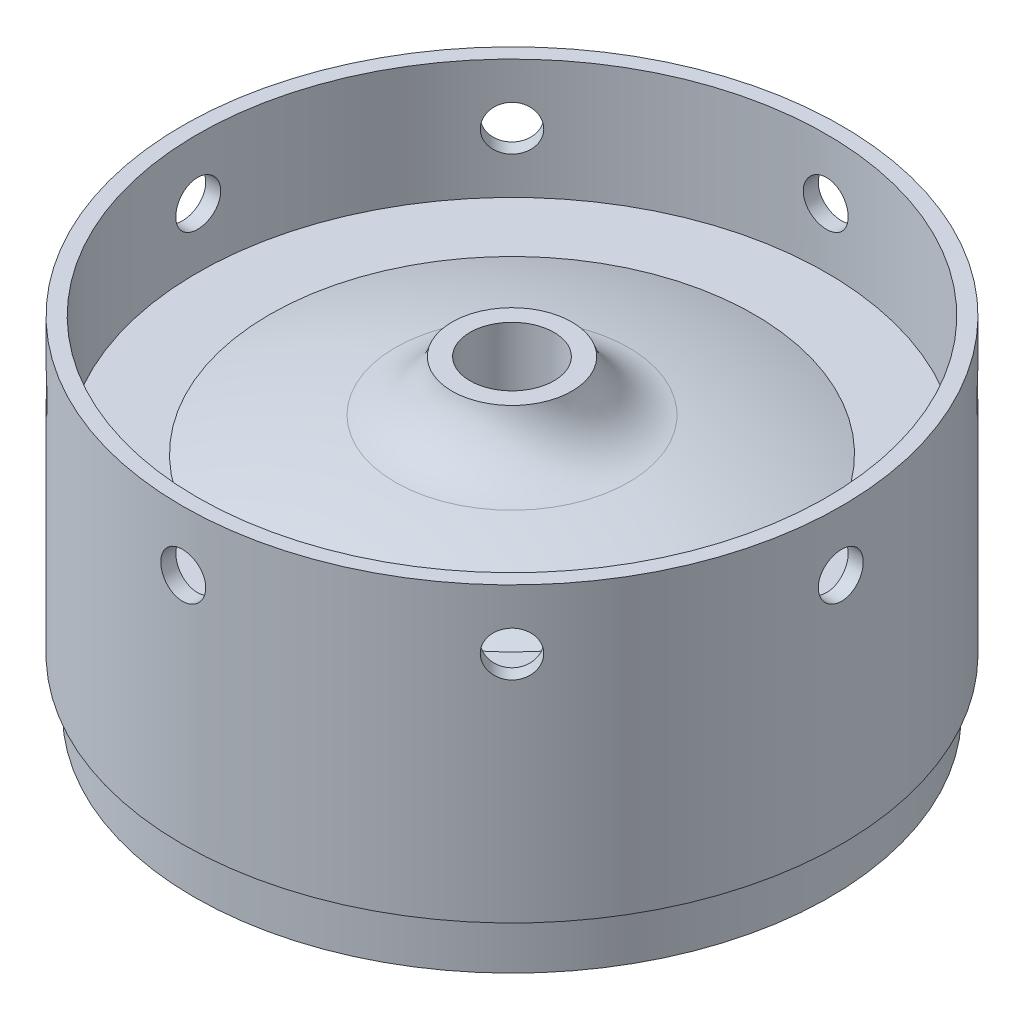
SolidWorks part; units mm, degrees
material "6061-T6 (SS)"
ref_plane "Front Plane" through (0, 0, 0) normal (0, 0, 1) x (1, 0, 0)
ref_plane "Top Plane" through (0, 0, 0) normal (0, 1, 0) x (1, 0, 0)
ref_plane "Right Plane" through (0, 0, 0) normal (1, 0, 0) x (0, 0, -1)
ref_axis "Axis1" through (0, 127.061, 0) along (0, -1, 0)
sketch "Sketch1" plane through (0, 0, 0) normal (0, 0, 1) x (1, 0, 0)
  line L0 (-69.85, 10.9548) -> (-69.85, 73.025)
  line L1 (-67.3735, 9.525) -> (-69.85, 10.9548)
  line L2 (0, 127.061) -> (0, -81.9141) construction
  line L3 (-8.9065, 65.553) -> (-12.7, 65.553)
  line L4 (-67.3735, 9.525) -> (-67.3735, 0)
  line L5 (-67.3735, 0) -> (-65.786, 0)
  line L6 (55, 0) -> (-55, 0) construction
  line L7 (-66.675, 73.025) -> (-69.85, 73.025)
  line L8 (-69.85, 10.9548) -> (-67.3735, 9.525)
  line L9 (-66.675, 47.625) -> (-51.3431, 47.625)
  line L11 (-66.675, 47.625) -> (-66.675, 73.025)
  line L14 (-8.9065, 65.553) -> (-8.9065, 50.313)
  line L15 (-65.786, 0) -> (-65.786, 9.525)
  line L16 (-65.786, 9.525) -> (-63.3918, 23.1034)
  arc A0 (-63.3918, 23.1034) -> (-51.3431, 40.8202) centre (-44.3418, 23.1034) cw
  arc A1 (-51.3431, 40.8202) -> (-8.9065, 50.313) centre (0, -89.1028) cw
  arc A2 (-24.7383, 54.8368) -> (-12.7, 65.553) centre (-27.3197, 69.8566) ccw
  arc A3 (-51.3431, 47.625) -> (-24.7383, 54.8368) centre (0, -89.1028) cw
  point P1 (0, 0)
  point P14 (-66.5798, 0)
  dimension "D5" = 19.05
  dimension "D6" = 139.7
  dimension "D7" = 146.05
  dimension "D8" = 63.5
  dimension "D12" = 15.24
  dimension "D2" = 170
  dimension "D3" = 9.525
  dimension "D4" = 1.5875
  dimension "D9" = 25.4
  dimension "D10" = 3.175
  dimension "D11" = 12.7
  dimension "D14" = 8.9065
  dimension "D15" = 4.064
  dimension "D16" = 69.85
  dimension "D17" = 120
  dimension "D18" = 15.24
revolve "Revolve2" add sketch "Sketch1" angle 360 about axis through (0, 127.061, 0) along (0, -1, 0) region at (-48.7191, 43.6439, 0)
sketch "Sketch2" plane through (0, 0, 0) normal (0, 0, 1) x (1, 0, 0)
  line L0 (0, 127.061) -> (0, -81.9141) construction
  line L1 (0, 87.1374) -> (-97.8719, 87.1374)
  line L2 (0, 87.1374) -> (0, -26.2798)
  line L3 (0, -26.2798) -> (-97.8719, -26.2798)
  line L4 (-97.8719, 87.1374) -> (-97.8719, -26.2798)
revolve "Cut-Revolve1" [suppressed] cut sketch "Sketch2" angle 315 about axis through (0, 127.061, 0) along (0, -1, 0)
ref_plane "Plane1" through (0, 60.325, 0) normal (0, 1, 0) x (1, 0, 0)
ref_axis "Axis2" through (0, 60.325, -76.835) along (0, 0, 1)
hole_wizard "3/8 (0.375) Diameter Hole1" positions "3DSketch3" profile "Sketch5" hole size "3/8" standard "ANSI Inch"
sketch3d "3DSketch3"
  line L0 (0, 60.325, -76.835) -> (0, 60.325, 76.835) construction
  point P0 (0, 60.325, 69.85)
  point P3 (0, 0, 0)
sketch "Sketch5" plane through (0, 60.325, 69.85) normal (1, 0, 0) x (0, -1, 0)
  line L0 (0, 0) -> (0, 14.5456)
  line L1 (0, 14.5456) -> (4.7625, 11.684)
  line L2 (4.7625, 11.684) -> (4.7625, 0)
  line L5 (4.7625, 0) -> (0, 0)
  line L10 (0, 14.5456) -> (-4.7625, 11.684) construction
  line L11 (0, -6.35) -> (0, 107.95) construction
  dimension "Hole Dia." = 9.525
  dimension "Hole Depth" = 11.684
  dimension "Drill Angle" = 118
pattern_circular "CirPattern1" count 8 over 360 about axis through (0, 127.061, 0) along (0, -1, 0) of "3/8 (0.375) Diameter Hole1"
